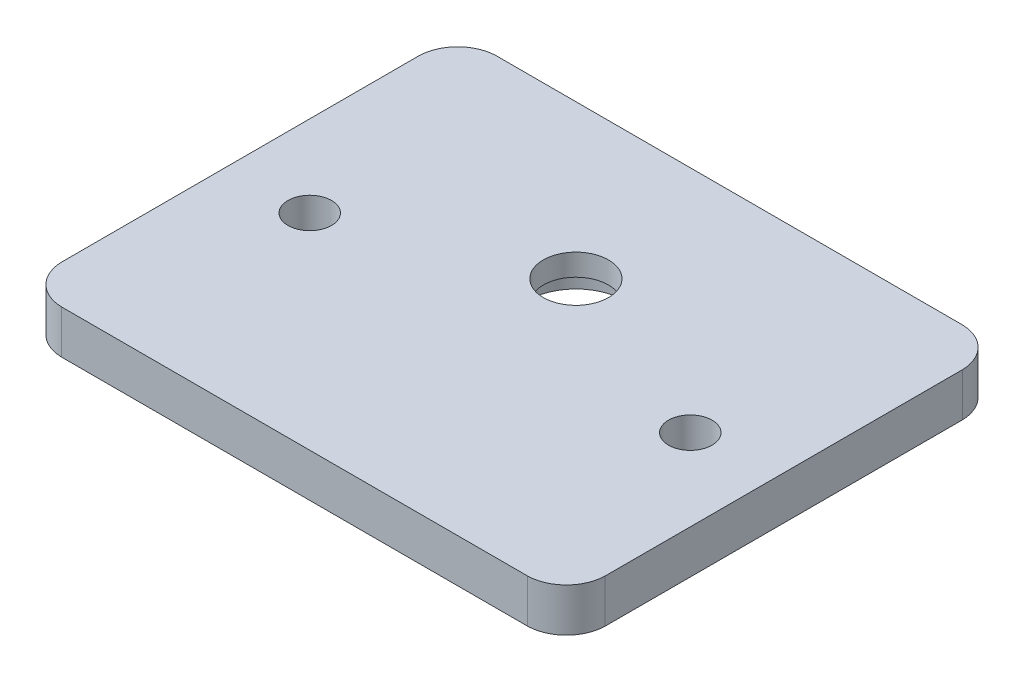
SolidWorks part; units mm, degrees
ref_plane "Front Plane" through (0, 0, 0) normal (0, 0, 1) x (1, 0, 0)
ref_plane "Top Plane" through (0, 0, 0) normal (0, 1, 0) x (1, 0, 0)
ref_plane "Right Plane" through (0, 0, 0) normal (1, 0, 0) x (0, 0, -1)
sketch "Sketch1" plane through (0, 0, 0) normal (0, 1, 0) x (1, 0, 0)
  line L0 (0, -3.7692) -> (0, -12.0494) construction
  line L5 (-25, 20) -> (25, 20)
  line L6 (-25, 20) -> (-25, -20)
  line L7 (-25, -20) -> (25, -20)
  line L8 (25, 20) -> (25, -20)
  line L9 (-25, 20) -> (25, -20) construction
  line L10 (-25, -20) -> (25, 20) construction
  line L11 (-5.3094, 0) -> (-10.9893, 0) construction
  arc A3 (-25, -16.277) -> (-21.447, -20) centre (-21.362, -16.362) ccw
  arc A4 (-25, 16.277) -> (-21.447, 20) centre (-21.362, 16.362) cw
  arc A5 (25, 16.277) -> (21.447, 20) centre (21.362, 16.362) ccw
  arc A6 (25, -16.277) -> (21.447, -20) centre (21.362, -16.362) cw
  circle A7 centre (-0.0217, 5.8999) radius 4.5
  circle A8 centre (0, 0) radius 14
  circle A9 centre (-17.5, -1.1027) radius 2
  circle A10 centre (17.5, -1.1027) radius 2
  circle A11 centre (-0.0217, 5.8999) radius 3
  point P0 (0, 0)
  dimension "D3" = 14.1001
  dimension "D1" = 50
  dimension "D2" = 40
extrude "Boss-Extrude2" add sketch "Sketch1" along normal blind 4 contours A6 L8 A5 L5 A4 L6 A3 L7 A10 A9 A8 | A8 A7 | A7 A11 | A11 region at (0, 0, -19.3597) region at (-4.3944, 0, -5.8999) region at (0.0025, 0, 0.6798) region at (-0.0217, 0, -5.8999)
extrude "Cut-Extrude2" cut sketch "Sketch1<14>" along normal through all contours A11
sketch "Sketch1<14>" plane through (0, 0, 0) normal (0, 1, 0) x (1, 0, 0) same geometry as "Sketch1"
extrude "Cut-Extrude3" cut sketch "Sketch1<15>" along normal blind 2 contours A7
sketch "Sketch1<15>" plane through (0, 0, 0) normal (0, 1, 0) x (1, 0, 0) same geometry as "Sketch1"
